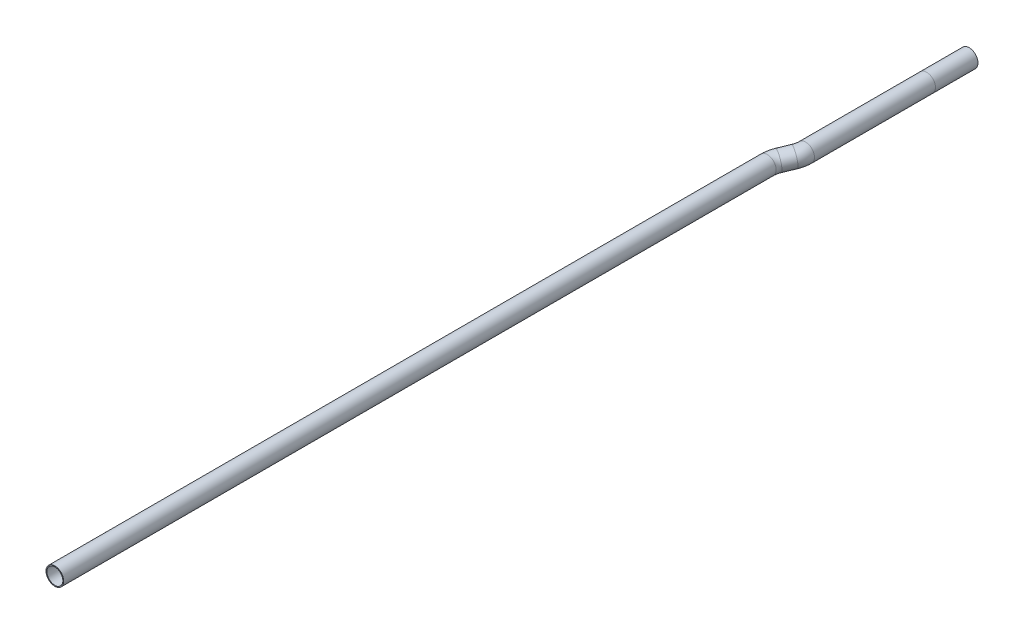
SolidWorks part; units mm, degrees
material "6061 Alloy"
ref_plane "Front Plane" through (0, 0, 0) normal (0, 0, 1) x (1, 0, 0)
ref_plane "Top Plane" through (0, 0, 0) normal (0, 1, 0) x (1, 0, 0)
ref_plane "Right Plane" through (0, 0, 0) normal (1, 0, 0) x (0, 0, -1)
sketch "Sketch1" plane through (0, 0, 0) normal (0, 0, 1) x (1, 0, 0)
  line L0 (0, 0) -> (3.7368, 0.7433) construction
  circle A0 centre (3.7368, 0.7433) radius 2.8575
  circle A1 centre (3.7368, 0.7433) radius 3.175
  dimension "D1" = 6.35
  dimension "D2" = 0.3175
ref_axis "Axis1" through (3.7368, 0.7433, -19.5915) along (0, 0, 1)
ref_plane "Plane1" through (0, 0, 0) normal (-0.1951, 0.9808, 0) x (0, 0, 1)
sketch "Sketch2" plane through (0, 0, 0) normal (-0.1951, 0.9808, 0) x (0, 0, 1)
  line L0 (0, 0) -> (0, 3.81) construction
  line L1 (0, 3.81) -> (-12.7, 3.81)
  line L2 (0, 3.81) -> (2.54, 3.81)
  line L3 (7.0301, 5.6699) -> (12.2004, 10.8401) construction
  line L4 (16.6905, 12.7) -> (37.9195, 12.7) construction
  line L5 (42.4096, 10.8401) -> (51.3899, 1.8599) construction
  line L6 (55.88, 0) -> (311.15, 0)
  line L8 (0, 0) -> (36.3164, 0) construction
  line L9 (290.83, 3.175) -> (290.83, -3.175) construction
  line L10 (76.2, 3.175) -> (76.2, -3.175) construction
  line L11 (0, 0.635) -> (0, 6.985) construction
  line L12 (2.54, 3.81) -> (45.8779, 3.81)
  line L13 (49.0529, 2.9593) -> (52.705, 0.8507)
  arc A0 (2.54, 3.81) -> (7.0301, 5.6699) centre (2.54, 10.16) ccw construction
  arc A1 (12.2004, 10.8401) -> (16.6905, 12.7) centre (16.6905, 6.35) cw construction
  arc A2 (37.9195, 12.7) -> (42.4096, 10.8401) centre (37.9195, 6.35) cw construction
  arc A3 (51.3899, 1.8599) -> (55.88, 0) centre (55.88, 6.35) ccw construction
  arc A4 (45.8779, 3.81) -> (49.0529, 2.9593) centre (45.8779, -2.54) cw
  arc A5 (52.705, 0.8507) -> (55.88, 0) centre (55.88, 6.35) ccw
  dimension "D3" = 6.35
  dimension "D4" = 6.35
  dimension "D5" = 6.35
  dimension "D6" = 6.35
  dimension "D13" = 6.35
  dimension "D14" = 6.35
  dimension "D1" = 3.81
  dimension "D2" = 12.7
  dimension "D7" = 20.32
  dimension "D8" = 12.7
  dimension "D9" = 135
  dimension "D10" = 135
  dimension "D11" = 20.32
  dimension "D12" = 2.54
  dimension "D15" = 30
sweep "Sweep1" add profiles "Sketch1" path "Sketch2"
